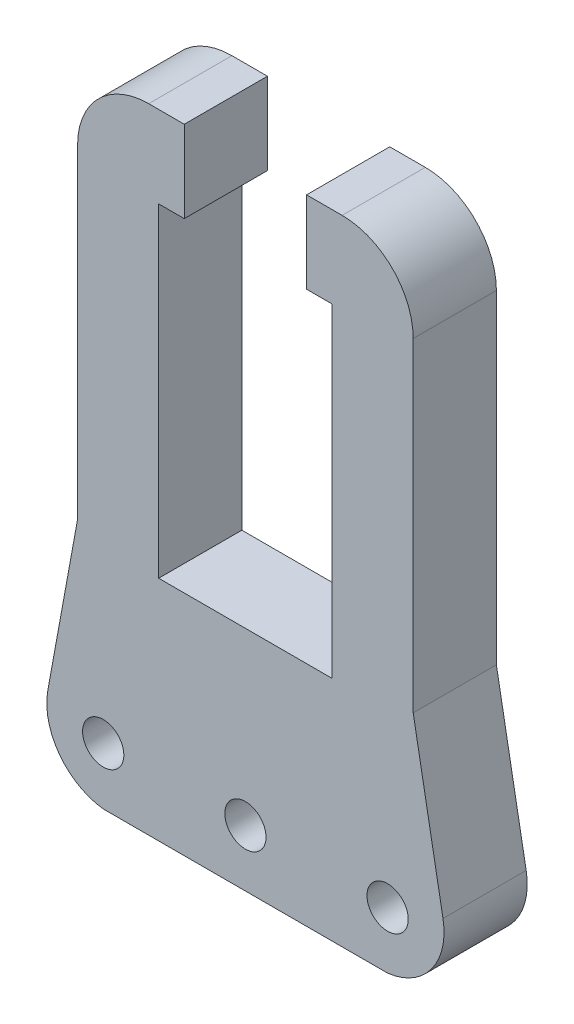
SolidWorks part; units mm, degrees
material "Acrylic (Medium-high impact)"
ref_plane "Front Plane" through (0, 0, 0) normal (0, 0, 1) x (1, 0, 0)
ref_plane "Top Plane" through (0, 0, 0) normal (0, 1, 0) x (1, 0, 0)
ref_plane "Right Plane" through (0, 0, 0) normal (1, 0, 0) x (0, 0, -1)
sketch "Model" plane through (0, 0, 0) normal (0, 0, 1) x (1, 0, 0)
  line L0 (519.9822, -457.799) -> (519.9822, 49542.201) construction
  line L1 (508.1822, 554.9348) -> (506.0873, 543.4616)
  line L2 (519.9822, 542.1848) -> (509.9822, 542.1848) construction
  line L3 (513.8822, 554.1848) -> (526.0822, 554.1848)
  line L4 (509.9822, 538.1848) -> (529.9822, 538.1848)
  line L5 (508.1822, 577.7348) -> (508.1822, 554.9348)
  line L6 (515.6822, 582.7348) -> (513.1822, 582.7348)
  line L7 (515.6822, 576.9848) -> (515.6822, 582.7348)
  line L8 (513.8822, 576.9848) -> (515.6822, 576.9848)
  line L9 (513.8822, 554.1848) -> (513.8822, 576.9848)
  line L10 (519.9822, 542.1848) -> (529.9822, 542.1848) construction
  line L80 (526.0822, 554.1848) -> (526.0822, 576.9848)
  line L81 (526.0822, 576.9848) -> (524.2822, 576.9848)
  line L82 (524.2822, 576.9848) -> (524.2822, 582.7348)
  line L83 (524.2822, 582.7348) -> (526.7822, 582.7348)
  line L84 (531.7822, 577.7348) -> (531.7822, 554.9348)
  line L85 (531.7822, 554.9348) -> (533.8772, 543.4616)
  circle A0 centre (509.9822, 542.1848) radius 1.45
  arc A1 (526.7822, 582.7348) -> (531.7822, 577.7348) centre (526.7822, 577.7348) cw
  arc A2 (506.0873, 543.4616) -> (509.9822, 538.1848) centre (510.5141, 542.6533) ccw
  arc A3 (533.8772, 543.4616) -> (529.9822, 538.1848) centre (529.4504, 542.6533) cw
  arc A4 (513.1822, 582.7348) -> (508.1822, 577.7348) centre (513.1822, 577.7348) ccw
  circle A5 centre (519.9822, 542.1848) radius 1.45
  circle A6 centre (529.9822, 542.1848) radius 1.45
  point P2 (519.9822, 554.1848)
  point P5 (519.9822, 538.1848)
  point P6 (519.9822, 554.1848)
  point P13 (519.9822, 538.1848)
  dimension "D4" = 2.9
  dimension "D9" = 4.5
  dimension "D11" = 5
  dimension "D1" = 12.2
  dimension "D2" = 22.8
  dimension "D3" = 10
  dimension "D5" = 4
  dimension "D6" = 12
  dimension "D7" = 5.75
  dimension "D8" = 1.8
  dimension "D10" = 11.4732
  dimension "D12" = 20
  dimension "D13" = 2.5
extrude "Boss-Extrude1" add sketch "Model" along normal blind 5.85
